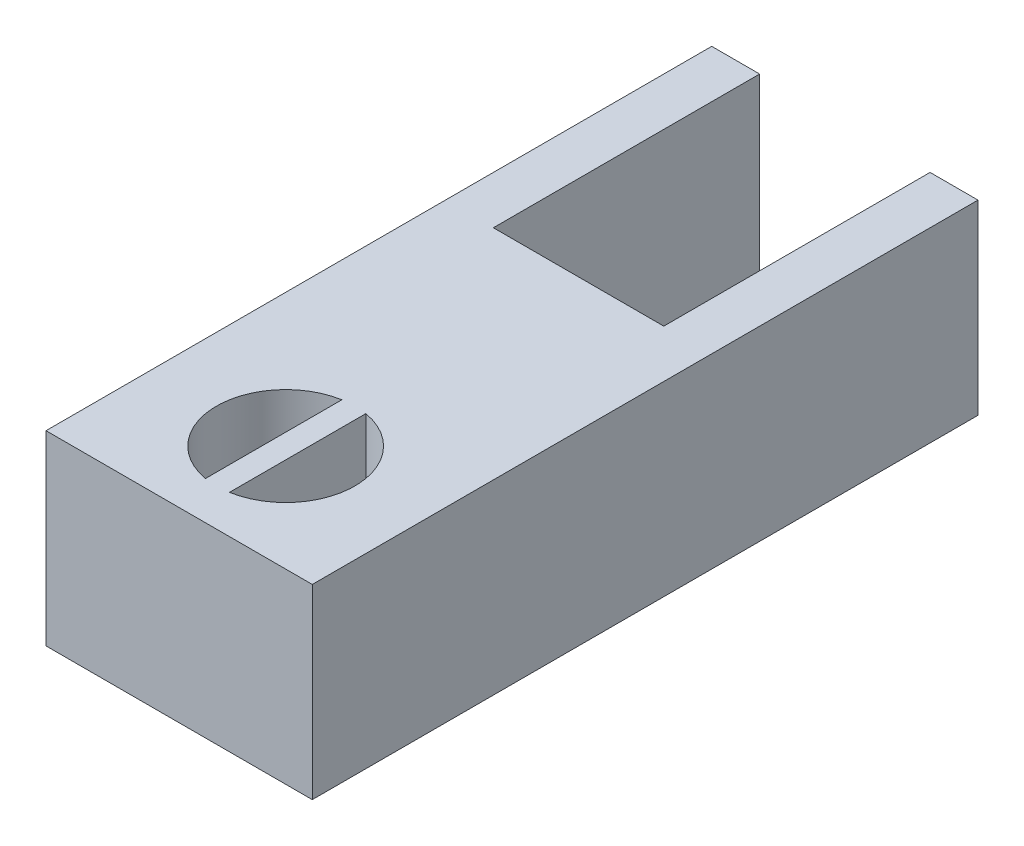
SolidWorks part; units mm, degrees
ref_plane "Front Plane" through (0, 0, 0) normal (0, 0, 1) x (1, 0, 0)
ref_plane "Top Plane" through (0, 0, 0) normal (0, 1, 0) x (1, 0, 0)
ref_plane "Right Plane" through (0, 0, 0) normal (1, 0, 0) x (0, 0, -1)
sketch "Sketch1" plane through (0, 0, 0) normal (0, 1, 0) x (1, 0, 0)
  line L1 (0, 0) -> (12.7, 0)
  line L2 (0, 0) -> (0, 31.75)
  line L3 (0, 31.75) -> (12.7, 31.75)
  line L4 (12.7, 0) -> (12.7, 31.75)
  dimension "D1" = 12.7
  dimension "D2" = 31.75
extrude "Boss-Extrude1" add sketch "Sketch1" along normal blind 8.89
sketch "Sketch2" plane through (0, 8.89, 0) normal (0, 1, 0) x (1, 0, 0)
  line L0 (12.7, 31.75) -> (0, 31.75) construction
  line L1 (2.286, 31.75) -> (10.414, 31.75)
  line L2 (2.286, 31.75) -> (2.286, 19.05)
  line L3 (2.286, 19.05) -> (10.414, 19.05)
  line L4 (10.414, 31.75) -> (10.414, 19.05)
  line L5 (0, 31.75) -> (0, 0) construction
  line L6 (12.7, 0) -> (12.7, 31.75) construction
  line L7 (0, 0) -> (12.7, 0) construction
  line L8 (6.35, 5.08) -> (6.35, 14.3202) construction
  line L9 (5.7785, 8.872) -> (6.9215, 8.872)
  line L10 (5.7785, 8.872) -> (5.7785, 1.0957)
  line L11 (5.7785, 1.0957) -> (6.9215, 1.0957)
  line L12 (6.9215, 8.872) -> (6.9215, 1.0957)
  circle A0 centre (6.35, 5.08) radius 3.302
  line M13 (12.7, 31.75) -> (0, 31.75)
  dimension "D3" = 6.604
  dimension "D1" = 8.128
  dimension "D2" = 2.286
  dimension "D4" = 6.35
  dimension "D5" = 5.08
  dimension "D6" = 12.7
  dimension "D7" = 1.143
  dimension "D8" = 0.5715
extrude "Cut-Extrude1" cut sketch "Sketch2" against normal blind 8.89 contours L4 L2 L3 M13 | L12 A0 | L10 A0 region at (6.35, 8.89, -25.4) region at (4.6351, 8.89, -5.08) region at (8.0649, 8.89, -5.08)
